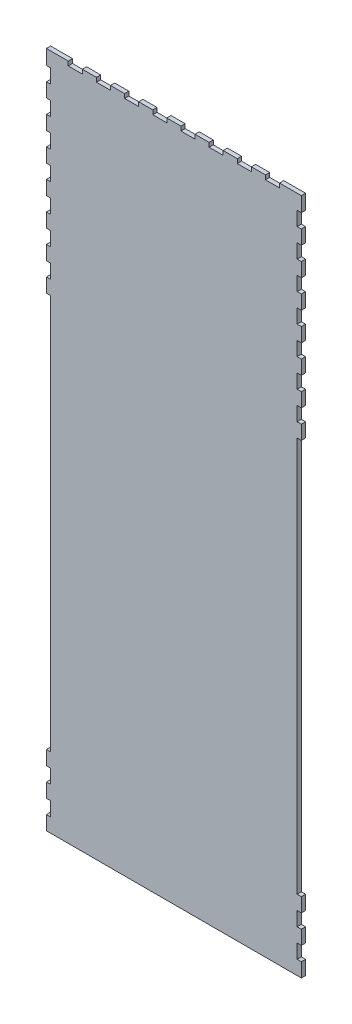
SolidWorks part; units mm, degrees
ref_plane "Front Plane" through (0, 0, 0) normal (0, 0, 1) x (1, 0, 0)
ref_plane "Top Plane" through (0, 0, 0) normal (0, 1, 0) x (1, 0, 0)
ref_plane "Right Plane" through (0, 0, 0) normal (1, 0, 0) x (0, 0, -1)
sketch "Sketch1" plane through (0, 0, 0) normal (0, 0, 1) x (1, 0, 0)
  line L2 (3, 408) -> (-12.5, 408)
  line L3 (-178, 408) -> (-178, 397.5)
  line L4 (-175, 0) -> (0, 0)
  line L5 (0, 0) -> (0, 405)
  line L6 (0, 405) -> (-175, 405)
  line L7 (-175, 405) -> (-175, 0)
  line L8 (-175, 0) -> (0, 0) construction
  line L10 (0, 405) -> (-175, 405) construction
  line L11 (-175, 405) -> (-175, 0) construction
  line L12 (-178, 397.5) -> (-175, 397.5)
  line L13 (-175, 397.5) -> (-175, 387.5)
  line L14 (-175, 387.5) -> (-178, 387.5)
  line L15 (-178, 387.5) -> (-178, 377.5)
  line L16 (-178, 408) -> (-178, -3) construction
  line L17 (-87.5, 408) -> (-87.5, -3) construction
  line L18 (-178, 377.5) -> (-175, 377.5)
  line L19 (-175, 377.5) -> (-175, 367.5)
  line L20 (-175, 367.5) -> (-178, 367.5)
  line L21 (-178, 357.5) -> (-175, 357.5)
  line L22 (-175, 357.5) -> (-175, 347.5)
  line L23 (-175, 347.5) -> (-178, 347.5)
  line L24 (-178, 337.5) -> (-175, 337.5)
  line L25 (-175, 337.5) -> (-175, 327.5)
  line L26 (-175, 327.5) -> (-178, 327.5)
  line L27 (-178, 317.5) -> (-175, 317.5)
  line L28 (-175, 317.5) -> (-175, 307.5)
  line L29 (-175, 307.5) -> (-178, 307.5)
  line L30 (-178, 297.5) -> (-175, 297.5)
  line L31 (-175, 297.5) -> (-175, 287.5)
  line L32 (-175, 287.5) -> (-178, 287.5)
  line L33 (-178, 277.5) -> (-175, 277.5)
  line L34 (-175, 277.5) -> (-175, 267.5)
  line L35 (-175, 267.5) -> (-178, 267.5)
  line L75 (-178, 367.5) -> (-178, 357.5)
  line L76 (-178, 347.5) -> (-178, 337.5)
  line L77 (-178, 327.5) -> (-178, 317.5)
  line L78 (-178, 307.5) -> (-178, 297.5)
  line L79 (-178, 287.5) -> (-178, 277.5)
  line L94 (3, -3) -> (3, 408) construction
  line L95 (0, 0) -> (0, 405) construction
  line L96 (0, 405) -> (0, 0) construction
  line L111 (3, 287.5) -> (3, 277.5)
  line L112 (3, 307.5) -> (3, 297.5)
  line L113 (3, 327.5) -> (3, 317.5)
  line L114 (3, 347.5) -> (3, 337.5)
  line L115 (3, 367.5) -> (3, 357.5)
  line L155 (0, 267.5) -> (3, 267.5)
  line L156 (0, 277.5) -> (0, 267.5)
  line L157 (3, 277.5) -> (0, 277.5)
  line L158 (0, 287.5) -> (3, 287.5)
  line L159 (0, 297.5) -> (0, 287.5)
  line L160 (3, 297.5) -> (0, 297.5)
  line L161 (0, 307.5) -> (3, 307.5)
  line L162 (0, 317.5) -> (0, 307.5)
  line L163 (3, 317.5) -> (0, 317.5)
  line L164 (0, 327.5) -> (3, 327.5)
  line L165 (0, 337.5) -> (0, 327.5)
  line L166 (3, 337.5) -> (0, 337.5)
  line L167 (0, 347.5) -> (3, 347.5)
  line L168 (0, 357.5) -> (0, 347.5)
  line L169 (3, 357.5) -> (0, 357.5)
  line L170 (0, 367.5) -> (3, 367.5)
  line L171 (0, 377.5) -> (0, 367.5)
  line L172 (3, 377.5) -> (0, 377.5)
  line L173 (3, 387.5) -> (3, 377.5)
  line L174 (0, 387.5) -> (3, 387.5)
  line L175 (0, 397.5) -> (0, 387.5)
  line L176 (3, 397.5) -> (0, 397.5)
  line L177 (3, 408) -> (3, 397.5)
  line L178 (-162.5, 408) -> (-162.5, 405)
  line L179 (-162.5, 405) -> (-152.5, 405)
  line L180 (-152.5, 405) -> (-152.5, 408)
  line L181 (-162.5, 408) -> (-178, 408)
  line L182 (3, 408) -> (-178, 408) construction
  line L183 (-142.5, 408) -> (-142.5, 405)
  line L184 (-132.5, 405) -> (-132.5, 408)
  line L185 (-142.5, 405) -> (-132.5, 405)
  line L186 (-122.5, 408) -> (-122.5, 405)
  line L187 (-112.5, 405) -> (-112.5, 408)
  line L188 (-122.5, 405) -> (-112.5, 405)
  line L189 (-102.5, 408) -> (-102.5, 405)
  line L190 (-92.5, 405) -> (-92.5, 408)
  line L191 (-102.5, 405) -> (-92.5, 405)
  line L192 (-82.5, 408) -> (-82.5, 405)
  line L193 (-72.5, 405) -> (-72.5, 408)
  line L194 (-82.5, 405) -> (-72.5, 405)
  line L195 (-62.5, 408) -> (-62.5, 405)
  line L196 (-52.5, 405) -> (-52.5, 408)
  line L197 (-62.5, 405) -> (-52.5, 405)
  line L198 (-42.5, 408) -> (-42.5, 405)
  line L199 (-32.5, 405) -> (-32.5, 408)
  line L200 (-42.5, 405) -> (-32.5, 405)
  line L201 (-22.5, 408) -> (-22.5, 405)
  line L202 (-12.5, 405) -> (-12.5, 408)
  line L203 (-22.5, 405) -> (-12.5, 405)
  line L204 (-142.5, 408) -> (-152.5, 408)
  line L205 (-122.5, 408) -> (-132.5, 408)
  line L206 (-102.5, 408) -> (-112.5, 408)
  line L207 (-82.5, 408) -> (-92.5, 408)
  line L208 (-62.5, 408) -> (-72.5, 408)
  line L209 (-42.5, 408) -> (-52.5, 408)
  line L210 (-22.5, 408) -> (-32.5, 408)
  line L211 (-178, 262.5) -> (-192.1885, 262.5) construction
  line L213 (-175, 247.5) -> (-178, 247.5) [skipped]
  line L214 (-178, 237.5) -> (-175, 237.5) [skipped]
  line L215 (-175, 237.5) -> (-175, 227.5) [skipped]
  line L216 (-175, 227.5) -> (-178, 227.5) [skipped]
  line L217 (-178, 217.5) -> (-175, 217.5) [skipped]
  line L218 (-175, 217.5) -> (-175, 207.5) [skipped]
  line L219 (-175, 207.5) -> (-178, 207.5) [skipped]
  line L220 (-178, 197.5) -> (-175, 197.5) [skipped]
  line L221 (-175, 197.5) -> (-175, 187.5) [skipped]
  line L222 (-175, 187.5) -> (-178, 187.5) [skipped]
  line L223 (-178, 177.5) -> (-175, 177.5) [skipped]
  line L224 (-175, 177.5) -> (-175, 167.5) [skipped]
  line L225 (-175, 167.5) -> (-178, 167.5) [skipped]
  line L226 (-178, 157.5) -> (-175, 157.5) [skipped]
  line L227 (-175, 157.5) -> (-175, 147.5) [skipped]
  line L228 (-175, 147.5) -> (-178, 147.5) [skipped]
  line L229 (-178, 137.5) -> (-175, 137.5) [skipped]
  line L230 (-175, 137.5) -> (-175, 127.5) [skipped]
  line L231 (-175, 127.5) -> (-178, 127.5) [skipped]
  line L232 (-178, 117.5) -> (-175, 117.5) [skipped]
  line L233 (-175, 117.5) -> (-175, 107.5) [skipped]
  line L234 (-175, 107.5) -> (-178, 107.5) [skipped]
  line L235 (-178, 97.5) -> (-175, 97.5) [skipped]
  line L236 (-175, 97.5) -> (-175, 87.5) [skipped]
  line L237 (-175, 87.5) -> (-178, 87.5) [skipped]
  line L238 (-178, 77.5) -> (-175, 77.5) [skipped]
  line L239 (-175, 77.5) -> (-175, 67.5) [skipped]
  line L240 (-175, 67.5) -> (-178, 67.5) [skipped]
  line L241 (-178, 57.5) -> (-175, 57.5) [skipped]
  line L242 (-175, 57.5) -> (-175, 47.5) [skipped]
  line L243 (-175, 47.5) -> (-178, 47.5) [skipped]
  line L244 (-178, 37.5) -> (-175, 37.5) [skipped]
  line L245 (-175, 37.5) -> (-175, 27.5) [skipped]
  line L246 (-175, 27.5) -> (-178, 27.5) [skipped]
  line L247 (-178, 17.5) -> (-175, 17.5) [skipped]
  line L248 (-175, 17.5) -> (-175, 7.5) [skipped]
  line L249 (-175, 7.5) -> (-178, 7.5) [skipped]
  line L250 (-175, 257.5) -> (-175, 247.5) [skipped]
  line L251 (-178, 257.5) -> (-175, 257.5) [skipped]
  line L254 (-178, -73) -> (3, -73)
  line L256 (-178, -3) -> (3, -3) construction
  line L257 (-178, -3) -> (3, -3) construction
  line L258 (-178, 267.5) -> (-178, 257.5)
  line L259 (-178, 257.5) -> (-175, 257.5)
  line L260 (3, 267.5) -> (3, 257.5)
  line L261 (3, 257.5) -> (0, 257.5)
  line L262 (-175, 257.5) -> (-175, 0)
  line L267 (0, 0) -> (0, 257.5)
  line L269 (-178, -23) -> (-175, -23)
  line L270 (-175, -23) -> (-175, 0)
  line L272 (3, -23) -> (0, -23)
  line L273 (0, -23) -> (0, 0)
  line L274 (-178, -33) -> (-175, -33)
  line L275 (-175, -33) -> (-175, -43)
  line L276 (-175, -43) -> (-178, -43)
  line L277 (-178, -43) -> (-178, -53)
  line L278 (-178, -53) -> (-175, -53)
  line L279 (-175, -53) -> (-175, -63)
  line L280 (-175, -63) -> (-178, -63)
  line L281 (-178, -33) -> (-178, -23)
  line L282 (-178, -73) -> (-178, -63)
  line L283 (3, -33) -> (0, -33)
  line L284 (0, -33) -> (0, -43)
  line L285 (0, -43) -> (3, -43)
  line L286 (3, -43) -> (3, -53)
  line L287 (3, -53) -> (0, -53)
  line L288 (0, -53) -> (0, -63)
  line L289 (0, -63) -> (3, -63)
  line L290 (3, -33) -> (3, -23)
  line L291 (3, -73) -> (3, -63)
  dimension "D3" = 10.5
  dimension "D4" = 10
  dimension "D6" = 10
  dimension "D7" = 10
  dimension "D8" = 15.5
  dimension "D10" = 10
  dimension "D11" = 481
  dimension "D12" = 10
  dimension "D13" = 50
  dimension "D14" = 50
  dimension "D15" = 3
  dimension "D16" = 3
  dimension "D17" = 3
  dimension "D18" = 10
  dimension "D19" = 10
  dimension "D20" = 10
  dimension "D21" = 10
  dimension "D22" = 10
  dimension "D23" = 10
  dimension "D24" = 10
  dimension "D25" = 10
  dimension "D26" = 10
  dimension "D27" = 10
  dimension "D28" = 10
  dimension "D1" = 0
  dimension "D2" = 3
  dimension "D5" = 20
  dimension "D9" = 8
extrude "Boss-Extrude1" add sketch "Sketch1" along normal blind 3
